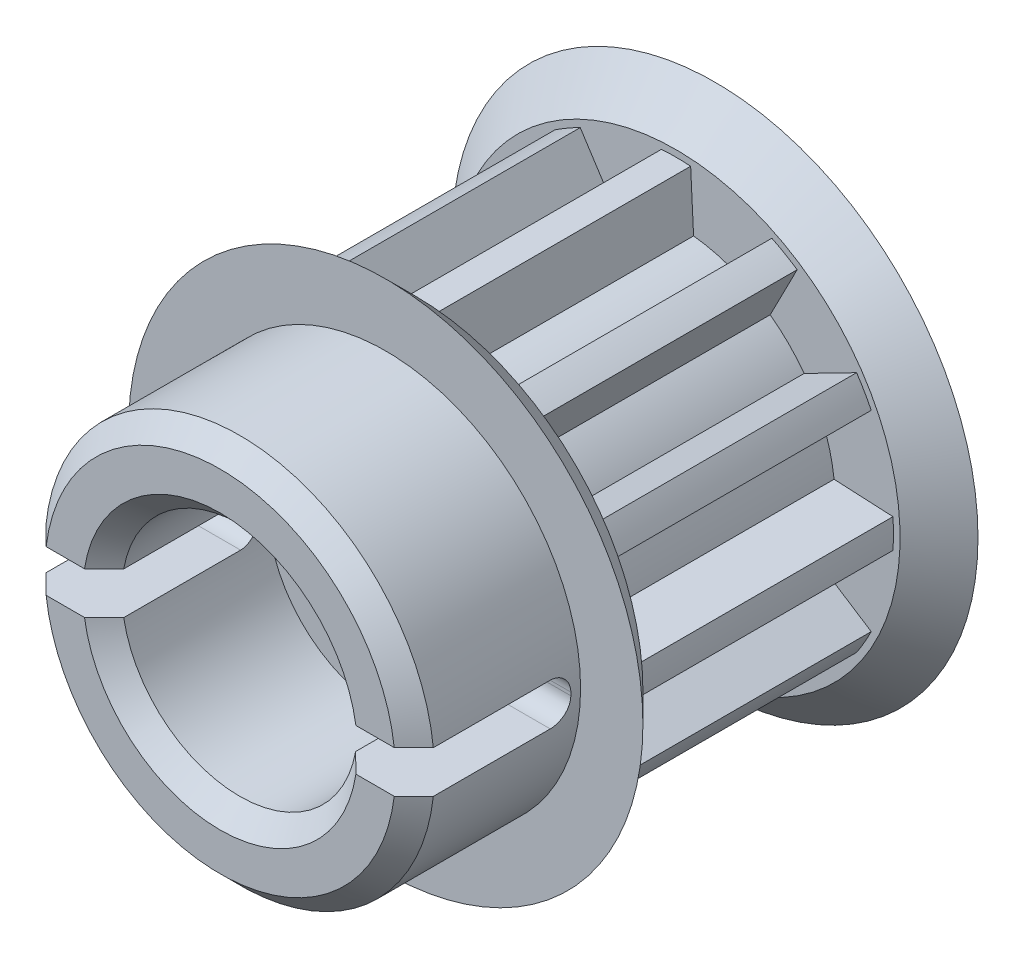
SolidWorks part; units mm, degrees
material "ABS"
ref_plane "Alzado" through (0, 0, 0) normal (0, 0, 1) x (1, 0, 0)
ref_plane "Planta" through (0, 0, 0) normal (0, 1, 0) x (1, 0, 0)
ref_plane "Vista lateral" through (0, 0, 0) normal (1, 0, 0) x (0, 0, -1)
sketch "Croquis1" plane through (0, 0, 0) normal (0, 0, 1) x (1, 0, 0)
  line L0 (0, 0) -> (0, 4.6049) construction
  line L1 (0.375, 5.5679) -> (0.45, 4.0556)
  line L2 (-0.375, 5.5679) -> (-0.45, 4.0556)
  line L3 (2.4592, 5.0094) -> (1.6381, 3.7373)
  line L4 (3.1087, 4.6344) -> (2.4175, 3.2873)
  line L5 (4.6344, 3.1087) -> (3.2873, 2.4175)
  line L6 (5.0094, 2.4592) -> (3.7373, 1.6381)
  line L7 (5.5679, 0.375) -> (4.0556, 0.45)
  line L8 (5.5679, -0.375) -> (4.0556, -0.45)
  line L9 (5.0094, -2.4592) -> (3.7373, -1.6381)
  line L10 (4.6344, -3.1087) -> (3.2873, -2.4175)
  line L11 (3.1087, -4.6344) -> (2.4175, -3.2873)
  line L12 (2.4592, -5.0094) -> (1.6381, -3.7373)
  line L13 (0.375, -5.5679) -> (0.45, -4.0556)
  line L14 (-0.375, -5.5679) -> (-0.45, -4.0556)
  line L15 (-2.4592, -5.0094) -> (-1.6381, -3.7373)
  line L16 (-3.1087, -4.6344) -> (-2.4175, -3.2873)
  line L17 (-4.6344, -3.1087) -> (-3.2873, -2.4175)
  line L18 (-5.0094, -2.4592) -> (-3.7373, -1.6381)
  line L19 (-5.5679, -0.375) -> (-4.0556, -0.45)
  line L20 (-5.5679, 0.375) -> (-4.0556, 0.45)
  line L21 (-5.0094, 2.4592) -> (-3.7373, 1.6381)
  line L22 (-4.6344, 3.1087) -> (-3.2873, 2.4175)
  line L23 (-3.1087, 4.6344) -> (-2.4175, 3.2873)
  line L24 (-2.4592, 5.0094) -> (-1.6381, 3.7373)
  circle A0 centre (0, 0) radius 1.8
  arc A1 (1.6381, 3.7373) -> (0.45, 4.0556) centre (0, 0) ccw
  arc A2 (3.1087, 4.6344) -> (2.4592, 5.0094) centre (0, 0) ccw
  arc A3 (5.0094, 2.4592) -> (4.6344, 3.1087) centre (0, 0) ccw
  arc A4 (5.5679, -0.375) -> (5.5679, 0.375) centre (0, 0) ccw
  arc A5 (4.6344, -3.1087) -> (5.0094, -2.4592) centre (0, 0) ccw
  arc A6 (2.4592, -5.0094) -> (3.1087, -4.6344) centre (0, 0) ccw
  arc A7 (-0.375, -5.5679) -> (0.375, -5.5679) centre (0, 0) ccw
  arc A8 (-3.1087, -4.6344) -> (-2.4592, -5.0094) centre (0, 0) ccw
  arc A9 (-5.0094, -2.4592) -> (-4.6344, -3.1087) centre (0, 0) ccw
  arc A10 (-5.5679, 0.375) -> (-5.5679, -0.375) centre (0, 0) ccw
  arc A11 (-4.6344, 3.1087) -> (-5.0094, 2.4592) centre (0, 0) ccw
  arc A12 (-2.4592, 5.0094) -> (-3.1087, 4.6344) centre (0, 0) ccw
  arc A13 (0.375, 5.5679) -> (-0.375, 5.5679) centre (0, 0) ccw
  arc A14 (3.2873, 2.4175) -> (2.4175, 3.2873) centre (0, 0) ccw
  arc A15 (4.0556, 0.45) -> (3.7373, 1.6381) centre (0, 0) ccw
  arc A16 (3.7373, -1.6381) -> (4.0556, -0.45) centre (0, 0) ccw
  arc A17 (2.4175, -3.2873) -> (3.2873, -2.4175) centre (0, 0) ccw
  arc A18 (0.45, -4.0556) -> (1.6381, -3.7373) centre (0, 0) ccw
  arc A19 (-1.6381, -3.7373) -> (-0.45, -4.0556) centre (0, 0) ccw
  arc A20 (-3.2873, -2.4175) -> (-2.4175, -3.2873) centre (0, 0) ccw
  arc A21 (-4.0556, -0.45) -> (-3.7373, -1.6381) centre (0, 0) ccw
  arc A22 (-3.7373, 1.6381) -> (-4.0556, 0.45) centre (0, 0) ccw
  arc A23 (-2.4175, 3.2873) -> (-3.2873, 2.4175) centre (0, 0) ccw
  arc A24 (-0.45, 4.0556) -> (-1.6381, 3.7373) centre (0, 0) ccw
  dimension "D1" = 0.9
  dimension "D2" = 3.6
  dimension "D4" = 1.5
  dimension "D3" = 0.75
  dimension "D6" = 1.23
  dimension "D5" = 12
extrude "Saliente-Extruir1" add sketch "Croquis1" along normal blind 6.7
sketch "Croquis2" plane through (0, 0, 6.7) normal (0, 0, 1) x (1, 0, 0)
  circle A0 centre (0, 0) radius 3.025
  circle A1 centre (0, 0) radius 5
  dimension "D1" = 10
  dimension "D2" = 6.05
extrude "Saliente-Extruir2" add sketch "Croquis2" along normal blind 5
chamfer "Chaflán1" distance 0.5 angle 45 1 edges at (5, 0, 11.7)
sketch "Croquis3" plane through (0, 0, 0) normal (0, 0, -1) x (-1, 0, 0)
  circle A0 centre (0, 0) radius 1.8
  circle A1 centre (0, 0) radius 6.75
  circle A2 centre (0, 0) radius 1.8 construction
  dimension "D1" = 13.5
extrude "Saliente-Extruir3" add sketch "Croquis3" along normal blind 1
chamfer "Chaflán2" distance 0.5 angle 45 1 edges at (3.025, 0, 11.7)
sketch "Croquis4" plane through (0, 0, 6.7) normal (0, 0, 1) x (1, 0, 0)
  circle A0 centre (0, 0) radius 1.8
  circle A1 centre (0, 0) radius 4.8926
  circle A2 centre (0, 0) radius 1.8 construction
extrude "Saliente-Extruir4" add sketch "Croquis4" along normal blind 0.1
chamfer "Chaflán3" distance 0.5 angle 45 12 edges at (3.9415, 1.0561, 6.7) (2.8853, 2.8853, 6.7) (1.0561, 3.9415, 6.7) (-1.0561, 3.9415, 6.7) (-2.8853, 2.8853, 6.7) (-3.9415, -1.0561, 6.7) (-3.9415, 1.0561, 6.7) (-2.8853, -2.8853, 6.7) (-1.0561, -3.9415, 6.7) (1.0561, -3.9415, 6.7) (2.8853, -2.8853, 6.7) (3.9415, -1.0561, 6.7)
chamfer "Chaflán4" distance 1 angle 45 1 edges at (-6.75, 0, 0)
sketch "Croquis6" plane through (0, 0, 6.7) normal (0, 0, 1) x (1, 0, 0)
  circle A0 centre (0, 0) radius 6.75
  circle A2 centre (0, 0) radius 1.8
  circle A4 centre (0, 0) radius 1.8 construction
  dimension "D1" = 13.5
extrude "Saliente-Extruir5" add sketch "Croquis6" along normal blind 0.75
chamfer "Chaflán5" distance 0.9 angle 45 1 edges at (6.75, 0, 6.7)
sketch "Croquis8" plane through (0, 0, -1) normal (0, 0, -1) x (-1, 0, 0)
  line L1 (-1.559, -2.4638) -> (1.3542, -2.5821)
  line L2 (1.3542, -2.5821) -> (2.9132, -0.1183)
  line L3 (2.9132, -0.1183) -> (1.559, 2.4638)
  line L4 (1.559, 2.4638) -> (-1.3542, 2.5821)
  line L5 (-1.3542, 2.5821) -> (-2.9132, 0.1183)
  line L6 (-2.9132, 0.1183) -> (-1.559, -2.4638)
  circle A0 centre (0, 0) radius 2.525 construction
  dimension "D1" = 5.05
extrude "Cortar-Extruir1" cut sketch "Croquis8" against normal blind 6.4
chamfer "Chaflán6" distance 1 angle 45 6 edges at (-0.1024, 2.5229, -1) (2.1337, 1.3502, -1) (2.2361, -1.1728, -1) (0.1024, -2.5229, -1) (-2.1337, -1.3502, -1) (-2.2361, 1.1728, -1)
chamfer "Chaflán7" distance 1 angle 45 1 edges at (-1.8, 0, 5.4)
sketch "Croquis9" plane through (0, 0, 11.7) normal (0, 0, 1) x (1, 0, 0)
  line L0 (5.7484, 0) -> (-6.3843, 0) construction
  line L1 (5.7026, -0.5408) -> (5.7026, 0.5408)
  line L2 (5.7026, 0.5408) -> (-5.9897, 0.5408)
  line L3 (-5.9897, 0.5408) -> (-5.9897, -0.5408)
  line L4 (-5.9897, -0.5408) -> (5.7026, -0.5408)
extrude "Cortar-Extruir2" cut sketch "Croquis9" along direction (0, 0, 1) on the side against the normal blind 4
fillet "Redondeo1" radius 0.5 4 edges at (3.9735, -0.5408, 7.7) (3.9735, 0.5408, 7.7) (-3.9735, -0.5408, 7.7) (-3.9735, 0.5408, 7.7)
